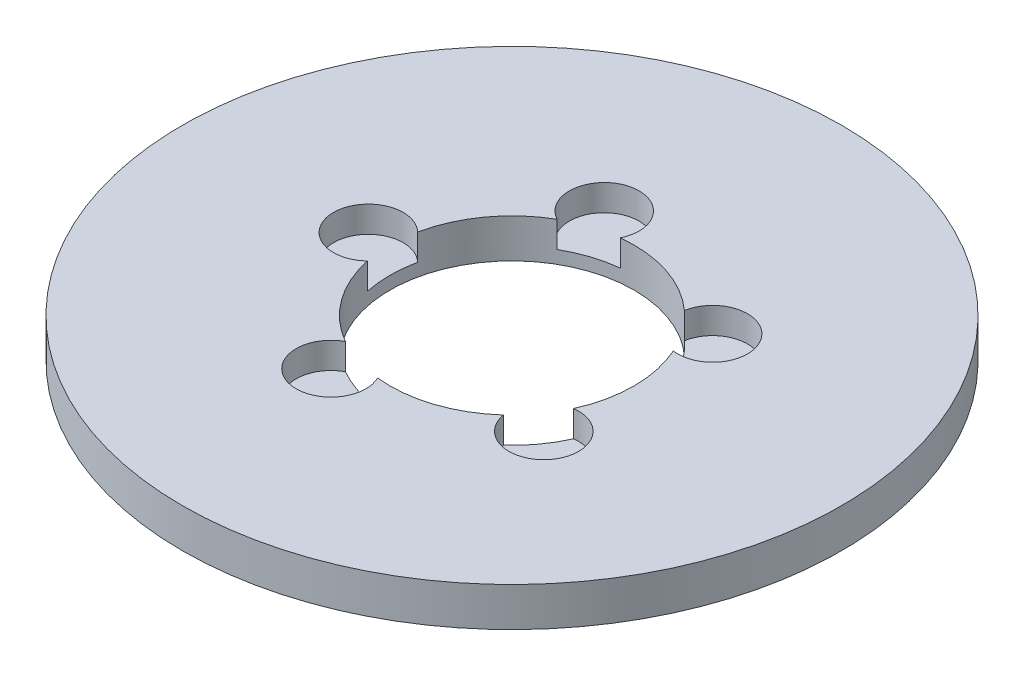
SolidWorks part; units mm, degrees
ref_plane "Front Plane" through (0, 0, 0) normal (0, 0, 1) x (1, 0, 0)
ref_plane "Top Plane" through (0, 0, 0) normal (0, 1, 0) x (1, 0, 0)
ref_plane "Right Plane" through (0, 0, 0) normal (1, 0, 0) x (0, 0, -1)
sketch "Sketch1" plane through (0, 0, 0) normal (0, 1, 0) x (1, 0, 0)
  circle A0 centre (0, 0) radius 67.5
  dimension "FLANGE_OD" = 135
extrude "Boss-Extrude1" add sketch "Sketch1" along normal blind 8
sketch "Sketch2" plane through (0, 0, 0) normal (0, 1, 0) x (1, 0, 0)
  circle A0 centre (0, 0) radius 25
  dimension "BORE_D" = 50
extrude "Cut-Extrude1" cut sketch "Sketch2" along normal through all
sketch "Sketch3" plane through (0, 8, 0) normal (0, 1, 0) x (1, 0, 0)
  circle A0 centre (0, 0) radius 29.4221 construction
  circle A1 centre (-29.4221, 0) radius 7.1384
  dimension "BOLT_D" = 14.2768
  dimension "BOLT_PCD" = 58.8442
extrude "Cut-Extrude2" cut sketch "Sketch3" against normal blind 5.366
pattern_circular "CirPattern1" count 5 over 360 about axis through (0, 0, 0) along (0, 1, 0) of "Cut-Extrude2"
